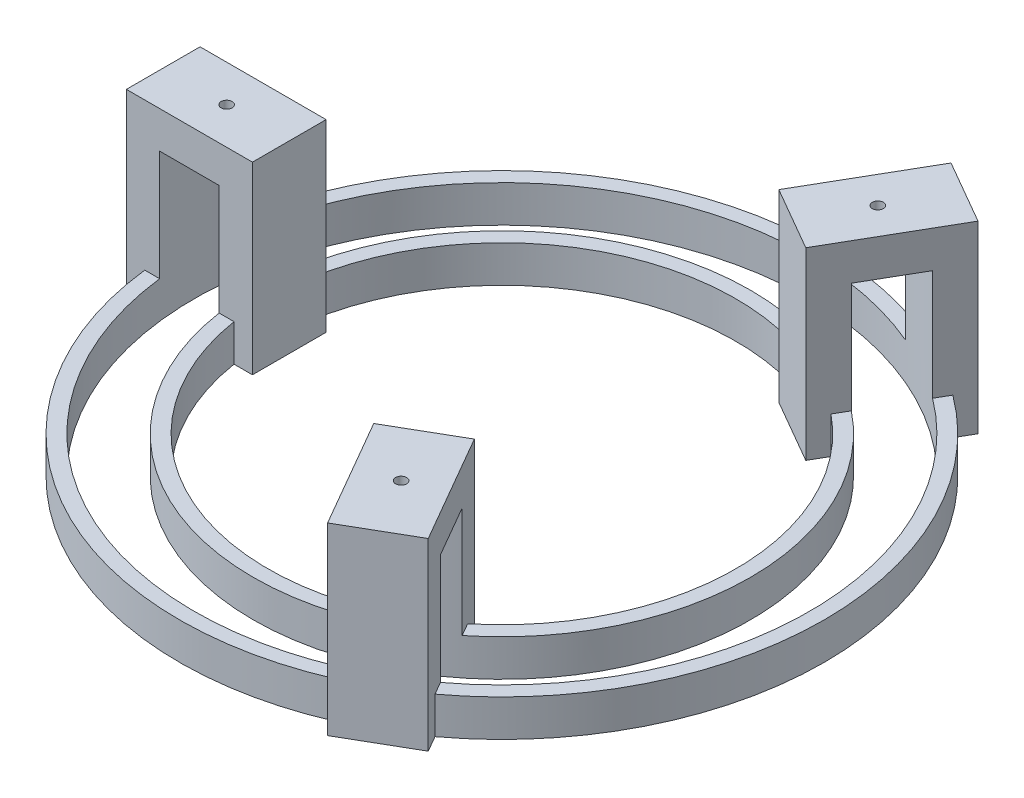
SolidWorks part; units mm, degrees
ref_plane "Ön Düzlem" through (0, 0, 0) normal (0, 0, 1) x (1, 0, 0)
ref_plane "Üst Düzlem" through (0, 0, 0) normal (0, 1, 0) x (1, 0, 0)
ref_plane "Sağ Düzlem" through (0, 0, 0) normal (1, 0, 0) x (0, 0, -1)
sketch "Çizim1" plane through (0, 0, 0) normal (0, 1, 0) x (1, 0, 0)
  line L0 (-62.7077, 10) -> (-57.7077, 10)
  line L1 (-57.7077, 10) -> (-57.7077, -10)
  line L2 (-57.7077, -10) -> (-62.7077, -10)
  line L3 (-91.9267, -10) -> (-86.9267, -10)
  line L4 (-91.9267, -10) -> (-91.9267, 10)
  line L5 (-91.9267, 10) -> (-86.9267, 10)
  line L6 (20.1936, 54.9763) -> (22.6936, 59.3064)
  line L7 (37.5141, 44.9763) -> (20.1936, 54.9763)
  line L8 (40.0141, 49.3064) -> (37.5141, 44.9763)
  line L9 (54.6236, 74.6109) -> (52.1236, 70.2807)
  line L10 (37.3031, 84.6109) -> (54.6236, 74.6109)
  line L11 (37.3031, 84.6109) -> (34.8031, 80.2807)
  line L12 (37.5141, -44.9763) -> (40.0141, -49.3064)
  line L13 (20.1936, -54.9763) -> (37.5141, -44.9763)
  line L14 (22.6936, -59.3064) -> (20.1936, -54.9763)
  line L15 (37.3031, -84.6109) -> (34.8031, -80.2807)
  line L16 (54.6236, -74.6109) -> (37.3031, -84.6109)
  line L17 (54.6236, -74.6109) -> (52.1236, -70.2807)
  arc A0 (-62.7077, -10) -> (22.6936, -59.3064) centre (0, 0) ccw
  circle A1 centre (0, 0) radius 67.5
  circle A2 centre (0, 0) radius 83.5
  arc A3 (-86.9267, -10) -> (34.8031, -80.2807) centre (0, 0) ccw
  arc A4 (40.0141, -49.3064) -> (40.0141, 49.3064) centre (0, 0) ccw
  arc A5 (22.6936, 59.3064) -> (-62.7077, 10) centre (0, 0) ccw
  arc A6 (34.8031, 80.2807) -> (-86.9267, 10) centre (0, 0) ccw
  arc A7 (52.1236, -70.2807) -> (52.1236, 70.2807) centre (0, 0) ccw
  point P33 (0, 0)
  dimension "D1" = 4
  dimension "D2" = 135
  dimension "D3" = 4
  dimension "D4" = 16
  dimension "D5" = 5
  dimension "D6" = 20
  dimension "D7" = 3
extrude "Yükseklik-Ekstrüzyon3" add sketch "Çizim1" along normal blind 10 contours A1 A5 L6 L7 L8 A4 L12 L13 L14 A0 L2 L1 L0 | L17 A7 L9 L10 L11 A6 L5 L4 L3 A3 L15 L16 A2 region at (-89.4203, 0, 0) region at (-65.5908, 0, 0)
sketch "Çizim2" plane through (0, 10, 0) normal (0, 1, 0) x (1, 0, 0)
  line L0 (-57.7077, 10) -> (-57.7077, -10) construction
  line L1 (-91.9267, 10) -> (-57.7077, 10)
  line L2 (-91.9267, 10) -> (-91.9267, -10)
  line L3 (-91.9267, -10) -> (-57.7077, -10)
  line L4 (-57.7077, 10) -> (-57.7077, -10)
  line L5 (-57.7077, -10) -> (-62.7077, -10) construction
  line L6 (37.5141, 44.9763) -> (20.1936, 54.9763)
  line L7 (54.6236, 74.6109) -> (37.5141, 44.9763)
  line L8 (54.6236, 74.6109) -> (37.3031, 84.6109)
  line L9 (37.3031, 84.6109) -> (20.1936, 54.9763)
  line L10 (20.1936, -54.9763) -> (37.5141, -44.9763)
  line L11 (37.3031, -84.6109) -> (20.1936, -54.9763)
  line L12 (37.3031, -84.6109) -> (54.6236, -74.6109)
  line L13 (54.6236, -74.6109) -> (37.5141, -44.9763)
  line L14 (40.0141, 49.3064) -> (37.5141, 44.9763) construction
  circle A0 centre (0, 0) radius 83.5
  circle A1 centre (0, 0) radius 67.5
  circle A2 centre (0, 0) radius 67.5 construction
  circle A3 centre (0, 0) radius 83.5 construction
  point P19 (0, 0)
  point P34 (0, 0)
  dimension "D1" = 3
extrude "Yükseklik-Ekstrüzyon6" add sketch "Çizim2" along normal blind 30 contours L1 A1 L3 L4 | L0 L3 L13 L1 | L7 A1 L9 L6 | L12 L9 L13 L7 L8 | L11 A1 L13 L10 | L10 L13 L11 L14 region at (-62.4825, 10, 0) region at (-87.6115, 10, 0) region at (31.2413, 10, -54.1115) region at (31.2413, 10, 54.1115) region at (43.8057, 10, -75.8738) region at (43.8057, 10, 75.8738)
extrude "Yükseklik-Ekstrüzyon7" add sketch "Çizim2<4>" along normal blind 10 from offset 30 contours L0 L3 L13 L1 | A1 L1 L13 L3 | L1 A1 L3 L4 | L7 A1 L9 L6 | A1 L7 L13 L9 | L12 L9 L13 L7 L8 | L11 A1 L13 L10 | A1 L11 L13 | L10 L13 L11 L14 region at (-62.4825, 10, 0) region at (-75.2756, 10, 0) region at (-87.6115, 10, 0) region at (31.2413, 10, -54.1115) region at (37.6378, 10, -65.1906) region at (37.6378, 10, 65.1906) region at (31.2413, 10, 54.1115) region at (43.8057, 10, -75.8738) region at (43.8057, 10, 75.8738)
sketch "Çizim2<4>" plane through (0, 10, 0) normal (0, 1, 0) x (1, 0, 0) same geometry as "Çizim2"
sketch "Çizim3" plane through (0, 50, 0) normal (0, 1, 0) x (1, 0, 0)
  line L0 (-57.7077, 10) -> (-57.7077, -10) construction
  circle A0 centre (-74.7077, 0) radius 1.5
  circle A1 centre (37.3538, 64.6987) radius 1.5
  circle A2 centre (37.3538, -64.6987) radius 1.5
  point P11 (0, 0)
  dimension "D1" = 3
  dimension "D2" = 17
  dimension "D3" = 3
extrude "Kes-Ekstrüzyon1" cut sketch "Çizim3" against normal blind 20
